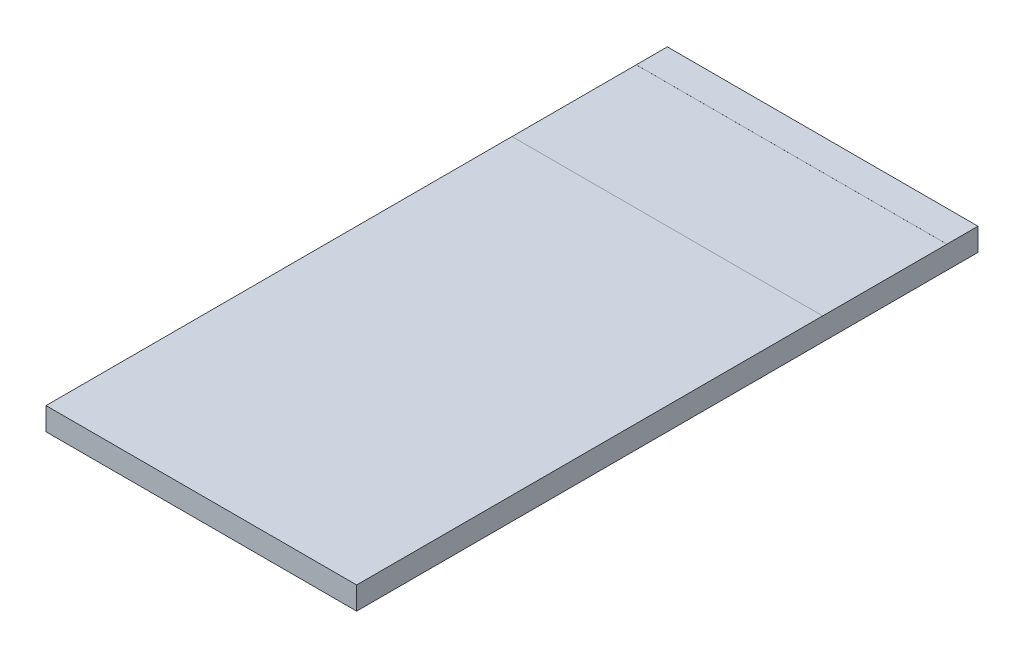
SolidWorks part; units mm, degrees
ref_plane "Top Plane" through (0, 0, 0) normal (0, 0, 1) x (1, 0, 0)
ref_plane "Front Plane" through (0, 0, 0) normal (0, 1, 0) x (1, 0, 0)
ref_plane "Right Plane" through (0, 0, 0) normal (1, 0, 0) x (0, 0, -1)
sketch "Sketch1" plane through (0, 0, 0) normal (0, 0, 1) x (1, 0, 0)
  line L1 (0, 0) -> (1, 0)
  line L2 (0, 0) -> (0, 0.0729)
  line L3 (0, 0.0729) -> (1, 0.0729)
  line L4 (1, 0) -> (1, 0.0729)
  dimension "D1" = 0.0729
  dimension "D2" = 1
extrude "Boss-Extrude1" add sketch "Sketch1" along normal blind 2 contours L3 L4 L1 L2
sketch "Sketch7" plane through (0, 0.0729, 0) normal (0, 1, 0) x (1, 0, 0)
  line L0 (0, -2) -> (0, 0) construction
  line L1 (1, 0) -> (0, 0)
  line L2 (1, 0) -> (1, -0.1)
  line L3 (1, -0.1) -> (0, -0.1)
  line L4 (0, 0) -> (0, -0.1)
  line L5 (1, -2) -> (1, 0) construction
  line L6 (1, -0.5) -> (0, -0.5)
  line L7 (1, -0.5) -> (1, -2)
  line L8 (1, -2) -> (0, -2)
  line L9 (0, -0.5) -> (0, -2)
  point P13 (0, -0.5)
  dimension "D1" = 0.1
  dimension "D2" = 0.5
  dimension "D3" = 2
extrude "Boss-Extrude6" add sketch "Sketch7" along normal blind 0.0001
extrude "Boss-Extrude7" add sketch "Sketch7<2>" against normal blind 0.0001 from vertex starting at point (0, 0, 0)
sketch "Sketch7<2>" plane through (0, 0.0729, 0) normal (0, 1, 0) x (1, 0, 0) same geometry as "Sketch7"
